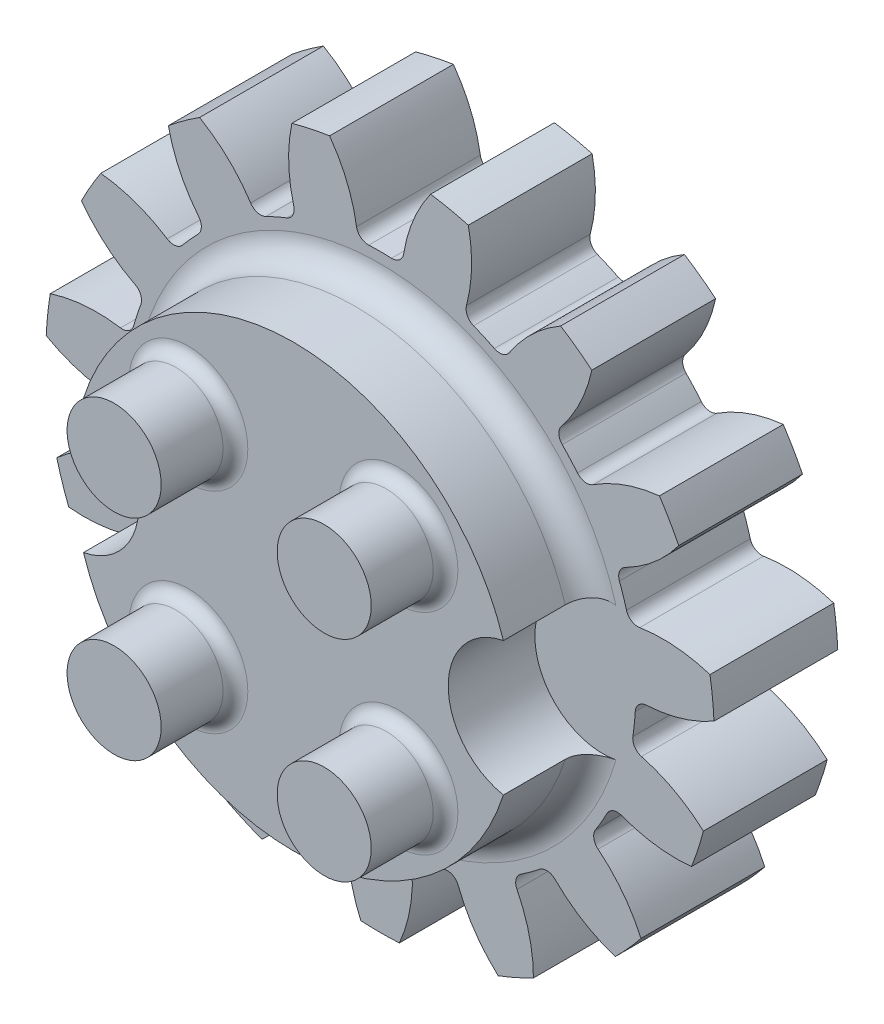
SolidWorks part; units mm, degrees
ref_plane "Front" through (0, 0, 0) normal (0, 0, 1) x (1, 0, 0)
ref_plane "Top" through (0, 0, 0) normal (0, 1, 0) x (1, 0, 0)
ref_plane "Right" through (0, 0, 0) normal (1, 0, 0) x (0, 0, -1)
sketch "Sketch1" plane through (0, 0, 0) normal (0, 0, 1) x (1, 0, 0)
  circle A0 centre (0, 0) radius 10.3235
  circle A1 centre (0, 0) radius 13.5
  circle A2 centre (0, 0) radius 11.9118
  dimension "D1" = 27
  dimension "D2" = 20.6471
  dimension "D3" = 23.8235
extrude "Boss-Extrude1" add sketch "Sketch1" along normal mid plane 5 contours A1
sketch "Sketch3" plane through (0, 0, 0) normal (0, 0, 1) x (1, 0, 0)
  line L0 (0, 0) -> (0, 13.5) construction
  line L1 (0, 0) -> (-0.8989, 10.2843) construction
  line L2 (-1.2451, 11.8465) -> (1.2451, 11.8465) construction
  line L3 (0, 8.4256) -> (-1.8029, 13.3791) construction
  line L4 (0, 0) -> (2.8068, 13.205) construction
  line L5 (1.2451, 11.8465) -> (3.6809, 11.3288) construction
  circle A7 centre (0, 0) radius 13.5 construction
  arc A10 (-2.0404, 13.3449) -> (-0.8989, 10.2843) centre (-7.003, 9.7508) cw
  arc A11 (2.0404, 13.3449) -> (0.8989, 10.2843) centre (7.003, 9.7508) ccw
  circle A12 centre (0, 0) radius 10.3235 construction
  arc A13 (-0.8989, 10.2843) -> (0.8989, 10.2843) centre (0, 0) cw
  arc A14 (-2.0404, 13.3449) -> (2.0404, 13.3449) centre (0, 0) cw
  circle A15 centre (0, 0) radius 11.9118 construction
  dimension "D1" = 20
  dimension "D2" = 12
extrude "Cut-Extrude1" cut sketch "Sketch3" against normal through all both and the other way through all
fillet "Fillet2" radius 0.4765 2 edges at (0.8989, 10.2843, 0) (-0.8989, 10.2843, 0)
pattern_circular "CirPattern1" count 15 over 360 about axis through (0, 0, 2.5) along (0, 0, -1) of "Cut-Extrude1", "Fillet2"
sketch "Sketch5" plane through (0, 0, 0) normal (0, 0, 1) x (1, 0, 0)
  circle A0 centre (0, 0) radius 1.25
  dimension "D1" = 2.5
extrude "Through_Center_Hole" cut sketch "Sketch5" against normal through all both and the other way through all
sketch "Sketch6" plane through (0, 0, 2.5) normal (0, 0, 1) x (1, 0, 0)
  line L0 (0, -9) -> (0, 9) construction
  line L1 (9, 0) -> (-9, 0) construction
  line L2 (-4.2426, -4.2426) -> (4.2426, 4.2426) construction
  line L3 (-4.2426, 4.2426) -> (4.2426, -4.2426) construction
  circle A0 centre (4.2426, 4.2426) radius 1.9 construction
  circle A1 centre (4.2426, -4.2426) radius 1.9 construction
  circle A2 centre (-4.2426, -4.2426) radius 1.9 construction
  circle A3 centre (-4.2426, 4.2426) radius 1.9 construction
  arc A4 (-8.4804, -2.7005) -> (-8.4804, 2.7005) centre (-9, 0) ccw
  arc A5 (8.4804, -2.7005) -> (8.4804, 2.7005) centre (9, 0) cw
  arc A6 (-8.4804, 2.7005) -> (8.4804, 2.7005) centre (0, 0) cw
  arc A7 (-8.4804, -2.7005) -> (8.4804, -2.7005) centre (0, 0) ccw
  dimension "D4" = 3.8
  dimension "D5" = 2.75
  dimension "D6" = 8.9
  dimension "D1" = 18
  dimension "D2" = 12
  dimension "D3" = 45
extrude "Boss-Extrude2" add sketch "Sketch6" along normal blind 3.5
sketch "Sketch7" plane through (0, 0, 6) normal (0, 0, 1) x (1, 0, 0)
  circle A0 centre (-4.2426, 4.2426) radius 1.9
  circle A1 centre (4.2426, 4.2426) radius 1.9
  circle A2 centre (4.2426, -4.2426) radius 1.9
  circle A3 centre (-4.2426, -4.2426) radius 1.9
  dimension "D1" = 3.8
extrude "Boss-Extrude3" add sketch "Sketch7" along normal blind 3
fillet "Fillet3" radius 1 2 edges at (0, -8.9, 2.5) (0, 8.9, 2.5)
fillet "Fillet4" radius 0.5 4 edges at (-2.3426, -4.2426, 6) (6.1426, -4.2426, 6) (6.1426, 4.2426, 6) (-2.3426, 4.2426, 6)
equation "\"od\"= 27'outside diameter"
equation "\"n\"= 15'number of teeth"
equation "\"m\"= \"od\" / ( \"n\" + 2 )'module"
equation "\"p\"= \"m\" * pi'pitch"
equation "\"d\"= \"m\" * \"n\"'primitive diameter"
equation "\"da\"= \"d\" + 2 * \"m\"'head diamater"
equation "\"df\"= \"d\" - 2 * \"m\"'foot diameter"
equation "\"D1@Sketch1\"=\"od\""
equation "\"D2@Sketch1\"=\"df\""
equation "\"D3@Sketch1\"=\"d\""
equation "\"D2@Sketch3\"=180/\"n\""
equation "\"D1@Fillet2\"=.3*\"m\""
equation "\"D1@CirPattern1\"=\"n\""
